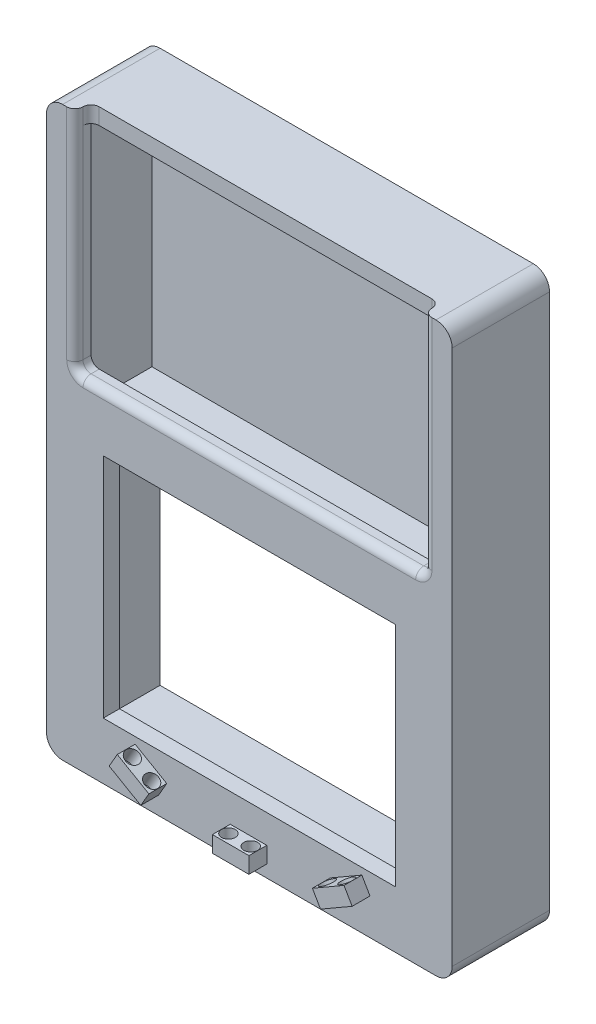
SolidWorks part; units mm, degrees
ref_plane "Piano frontale" through (0, 0, 0) normal (0, 0, 1) x (1, 0, 0)
ref_plane "Piano superiore" through (0, 0, 0) normal (0, 1, 0) x (1, 0, 0)
ref_plane "Piano destro" through (0, 0, 0) normal (1, 0, 0) x (0, 0, -1)
sketch "Schizzo1" plane through (0, 0, 0) normal (0, 0, 1) x (1, 0, 0)
  line L0 (0, 0) -> (0, -700)
  line L1 (0, 0) -> (500, 0)
  line L2 (500, 0) -> (500, -700)
  line L3 (500, -700) -> (0, -700)
  line L8 (20, -20) -> (480, -20)
  line L9 (480, -20) -> (480, -680)
  line L10 (480, -680) -> (20, -680)
  line L11 (20, -20) -> (20, -680)
  dimension "D1" = 700
  dimension "D2" = 500
  dimension "D3" = 20
extrude "Estrusione-Estrusione4" add sketch "Schizzo1" along normal blind 20 contours L3 L0 L1 L2
extrude "Estrusione-Estrusione5" add sketch "Schizzo1<4>" against normal blind 100
sketch "Schizzo1<4>" plane through (0, 0, 0) normal (0, 0, 1) x (1, 0, 0) same geometry as "Schizzo1"
sketch "Schizzo2" plane through (0, 0, 0) normal (0, 0, 1) x (1, 0, 0)
  line L4 (148.2503, -660.67) -> (138.2491, -677.9899)
  line L5 (226.5, -665) -> (271.5, -665)
  line L6 (226.5, -665) -> (226.5, -685)
  line L7 (226.5, -685) -> (271.5, -685)
  line L8 (271.5, -685) -> (271.5, -665)
  line L10 (109.2791, -638.17) -> (99.2791, -655.4905)
  line L11 (99.2791, -655.4905) -> (138.2491, -677.9899)
  line L14 (109.2791, -638.17) -> (148.2503, -660.67)
  line L21 (99.2791, -655.4905) -> (138.2491, -677.9899)
  line L23 (359.75, -677.9899) -> (398.7211, -655.4899)
  line L24 (388.7211, -638.1694) -> (398.7211, -655.4899)
  line L25 (349.75, -660.6694) -> (388.7211, -638.1694)
  line L28 (359.75, -677.9899) -> (349.75, -660.6694)
  dimension "D1" = 45
  dimension "D2" = 45
  dimension "D3" = 45
  dimension "D4" = 20
  dimension "D5" = 20
  dimension "D6" = 20
extrude "Estrusione-Estrusione6" add sketch "Schizzo2" along normal offset from surface (22 mm away) 22 from surface separate body contours L14 L10 L11 L4 | L7 L8 L5 L6 region at (123.7645, -658.0801, 0) region at (249, -675, 0) up to face at (250, -350, 20) offset beyond the face yes starting at face at (250, -350, 20)
extrude "Estrusione-Estrusione7" add sketch "Schizzo2<3>" along normal blind 22 from surface contours L23 L24 L25 L28 starting at face at (250, -350, 20)
sketch "Schizzo2<3>" plane through (0, 0, 0) normal (0, 0, 1) x (1, 0, 0) same geometry as "Schizzo2"
sketch "Schizzo6" plane through (-259.0159, -448.6288, 0) normal (-0.5, -0.866, 0) x (0.866, -0.5, 0)
  line L0 (436.2229, 42) -> (436.2229, 20) construction
  line L1 (458.7222, 42) -> (413.7235, 42) construction
  line L2 (413.7235, 20) -> (458.7222, 20) construction
  line L3 (422.4729, 31) -> (449.9729, 31) construction
  circle A0 centre (422.4729, 31) radius 8.5
  circle A1 centre (449.9729, 31) radius 8.5
  point P9 (436.2229, 31)
extrude "Taglio-Estrusione1" cut sketch "Schizzo6" against normal blind 22
sketch "Schizzo7" plane through (0, -685, 0) normal (0, -1, 0) x (1, 0, 0)
  line L0 (249, 42) -> (249, 20) construction
  line L1 (271.5, 42) -> (226.5, 42) construction
  line L2 (226.5, 20) -> (271.5, 20) construction
  line L3 (235.25, 31) -> (262.75, 31) construction
  circle A0 centre (235.25, 31) radius 8.5
  circle A1 centre (262.75, 31) radius 8.5
  point P9 (249, 31)
extrude "Taglio-Estrusione2" cut sketch "Schizzo7" against normal blind 22
sketch "Schizzo8" plane through (383.5157, -664.2687, 0) normal (0.5, -0.866, 0) x (0.866, 0.5, 0)
  line L0 (-4.9423, 42) -> (-4.9423, 20) construction
  line L1 (-27.4423, 42) -> (17.5577, 42) construction
  line L2 (-27.4423, 20) -> (17.5577, 20) construction
  line L3 (-18.6923, 31) -> (8.8077, 31) construction
  circle A0 centre (-18.6923, 31) radius 8.5
  circle A2 centre (8.8077, 31) radius 8.5
  point P9 (-4.9423, 31)
extrude "Taglio-Estrusione3" cut sketch "Schizzo8" against normal blind 22
sketch "Schizzo10" plane through (0, 0, 20) normal (0, 0, 1) x (1, 0, 0)
  line L10 (70, -350) -> (430, -350)
  line L14 (70, -630) -> (430, -630)
  line L15 (430, -630) -> (430, -70)
  line L16 (70, -70) -> (70, -630)
  line L17 (430, -70) -> (70, -70)
  line L18 (70, -630) -> (430, -630)
  line L19 (430, -630) -> (430, -350)
  line L20 (70, -350) -> (70, -630)
  dimension "D2" = 360
  dimension "D3" = 560
  dimension "D1" = 70
extrude "Taglio-Estrusione4" cut sketch "Schizzo10" against normal blind 22
fillet "Raccordo1" radius 20 1 edges at (0, 0, -40) type face fillet first side face at (250, 0, -40) second side face at (0, -350, -40)
fillet "Raccordo2" radius 20 1 edges at (500, 0, -40) type face fillet first side face at (260, 0, -40) second side face at (500, -350, -40)
fillet "Raccordo3" radius 20 1 edges at (500, -700, -40) type face fillet first side face at (500, -360, -40) second side face at (250, -700, -40)
fillet "Raccordo4" radius 20 1 edges at (0, -700, -40) type face fillet first side face at (0, -360, -40) second side face at (240, -700, -40)
sketch "Schizzo11" plane through (0, 0, -100) normal (0, 0, -1) x (-1, 0, 0)
  line L0 (-480, -350) -> (-20, -350)
  line L1 (-480, -680) -> (-480, -20) construction
  line L2 (-20, -20) -> (-20, -680) construction
  line L3 (-20, -350) -> (-20, -20)
  line L4 (-20, -20) -> (-480, -20)
  line L5 (-480, -20) -> (-480, -350)
  line L6 (-480, -350) -> (-480, -335)
  line L7 (-480, -335) -> (-20, -335)
  line L8 (-20, -335) -> (-20, -350)
  line L9 (-480, -350) -> (-20, -350)
  line M1 (-20, -20) -> (-20, -680)
  line M3 (-480, -680) -> (-480, -20)
  line M4 (-480, -20) -> (-20, -20)
extrude "Estrusione-Estrusione8" add sketch "Schizzo11" against normal up to surface (100 mm away) contours L7 L0 L3 M3 region at (250, -342.5, -100) up to face at (250, -490, 0)
extrude "Estrusione-Estrusione9" add sketch "Schizzo11<3>" against normal blind 10 contours L5 L7 M1 M4 region at (250, -177.5, -100)
sketch "Schizzo11<3>" plane through (0, 0, -100) normal (0, 0, -1) x (-1, 0, 0) same geometry as "Schizzo11"
sketch "Schizzo12" plane through (0, 0, 20) normal (0, 0, 1) x (1, 0, 0)
  line L0 (35, -35) -> (35, 0)
  line L2 (35, -280) -> (35, -35)
  line L4 (465, -35) -> (465, -280)
  line L5 (20, 0) -> (480, 0) construction
  line L7 (465, -35) -> (465, 0)
  line L8 (465, 0) -> (35, 0)
  line L12 (35, -280) -> (465, -280)
extrude "Taglio-Estrusione5" cut sketch "Schizzo12" against normal blind 20
fillet "Raccordo5" radius 10 1 edges at (35, -280, 10) type face fillet first side face at (250, -280, 10) second side face at (35, -116, 8)
fillet "Raccordo6" radius 10 1 edges at (465, -280, 10) type face fillet first side face at (255, -280, 10) second side face at (465, -116, 8)
fillet "Raccordo7" radius 10 1 edges at (465, -10, 0) type face fillet first side face at (465, -112, 8) second side face at (250, -10, 0)
fillet "Raccordo8" radius 10 1 edges at (35, -10, 0) type face fillet first side face at (35, -112, 8) second side face at (245, -10, 0)
fillet "Raccordo9" radius 10 1 edges at (465, -135, 20) type face fillet first side face at (250, -490, 20) second side face at (465, -96.6667, 10)
